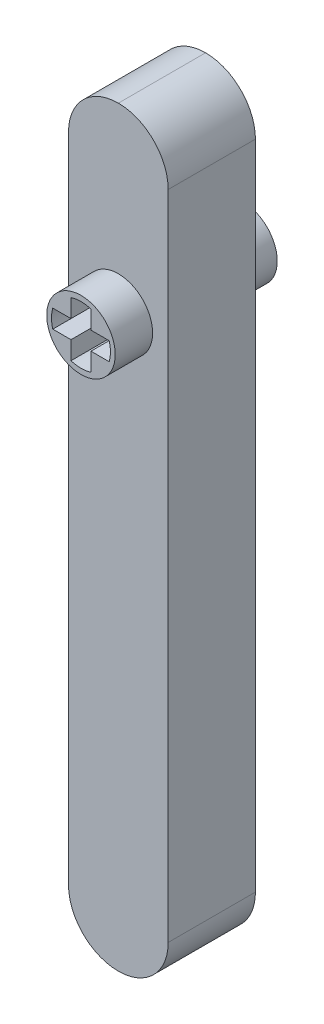
SolidWorks part; units mm, degrees
ref_plane "Front Plane" through (0, 0, 0) normal (0, 0, 1) x (1, 0, 0)
ref_plane "Top Plane" through (0, 0, 0) normal (0, 1, 0) x (1, 0, 0)
ref_plane "Right Plane" through (0, 0, 0) normal (1, 0, 0) x (0, 0, -1)
sketch "Sketch1" plane through (0, 0, 0) normal (0, 0, 1) x (1, 0, 0)
  line L0 (4, 25.4) -> (4, 34.925)
  line L2 (-4, 25.4) -> (-4, -25.4)
  line L3 (-4, -25.4) -> (4, -25.4)
  line L4 (4, 25.4) -> (4, -25.4)
  line L5 (-4, 25.4) -> (4, -25.4) construction
  line L6 (-4, -25.4) -> (4, 25.4) construction
  line L7 (4, 34.925) -> (-4, 34.925)
  line L8 (-4, 34.925) -> (-4, 25.4)
  line L9 (-4, 25.4) -> (4, 25.4) construction
  point P0 (0, 0)
  dimension "D1" = 8
  dimension "D2" = 50.8
  dimension "D3" = 34.925
extrude "Boss-Extrude1" add sketch "Sketch1" along normal blind 7
fillet "Fillet1" radius 4 4 edges at (-4, -25.4, 3.5) (4, -25.4, 3.5) (4, 34.925, 3.5) (-4, 34.925, 3.5)
sketch "Sketch2" plane through (0, 0, 7) normal (0, 0, 1) x (1, 0, 0)
  circle A0 centre (0, 20.32) radius 2.75
  dimension "D1" = 5.5
  dimension "D2" = 20.32
extrude "Boss-Extrude2" add sketch "Sketch2" along normal blind 3 and the other way blind 10
sketch "Sketch3" plane through (0, 0, -3) normal (0, 0, -1) x (-1, 0, 0)
  line L2 (-0.8, 21.0514) -> (-0.8, 22.5141)
  line L3 (0.8, 22.5141) -> (0.8, 21.0514)
  line L10 (-0.8, 21.0514) -> (0.8, 21.0514) construction
  line L11 (-0.8, 21.0514) -> (-0.8, 19.5886) construction
  line L13 (-2.2627, 19.5886) -> (-0.8, 19.5886)
  line L14 (-0.8, 19.5886) -> (-0.8, 18.1259)
  line L15 (0.8, 18.1259) -> (0.8, 19.5886)
  line L16 (0.8, 19.5886) -> (2.2627, 19.5886)
  line L18 (2.2627, 21.0514) -> (-3.442, 21.0514)
  circle A5 centre (0, 20.32) radius 2.7431 construction
  arc A6 (-0.8, 22.5141) -> (0.8, 22.5141) centre (0, 20.0402) cw
  arc A7 (-2.2627, 21.0514) -> (-2.2627, 19.5886) centre (0.2323, 20.32) ccw
  arc A8 (-0.8, 18.1259) -> (0.8, 18.1259) centre (0, 20.5998) ccw
  arc A9 (2.2627, 21.0514) -> (2.2627, 19.5886) centre (-0.2323, 20.32) cw
  point P6 (0, 21.0514)
  point P20 (-2.3677, 20.32)
  point P21 (0, 17.9998)
  point P22 (0, 0)
  point P23 (0, 20.32)
  dimension "D2" = 1.6
  dimension "D3" = 2.6
  dimension "D1" = 1.4627
extrude "Cut-Extrude1" cut sketch "Sketch3" against normal through all contours A9 L18 A7 L13 L14 A8 L15 L16 | A6 L2 L18 L3 region at (0, 21.8254, -3) region at (0, 19.9193, -3)
